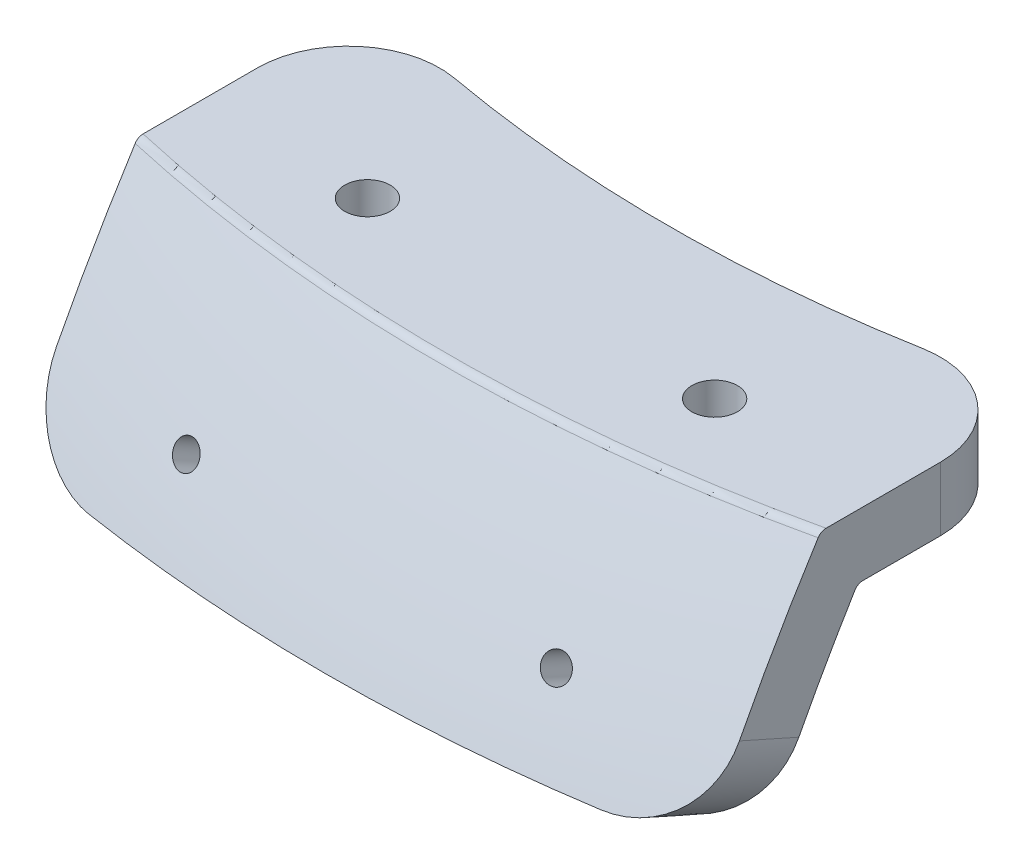
SolidWorks part; units mm, degrees
material "Polyether Polyol"
ref_plane "Front Plane" through (0, 0, 0) normal (0, 0, 1) x (1, 0, 0)
ref_plane "Top Plane" through (0, 0, 0) normal (0, 1, 0) x (1, 0, 0)
ref_plane "Right Plane" through (0, 0, 0) normal (1, 0, 0) x (0, 0, -1)
sketch "Sketch1" plane through (0, 0, 0) normal (1, 0, 0) x (0, 0, -1)
  line L0 (-182.3577, 155.0626) -> (-175.976, 152.1862) construction
  line L1 (-169.6296, 178.8688) -> (-144.7872, 178.8688) construction
  line L9 (-144.7872, 178.8688) -> (-144.7872, 171.8688) construction
  line L10 (-144.7872, 171.8688) -> (-165.7041, 171.8688) construction
  line L11 (-182.3577, 155.0626) -> (-175.976, 152.1862)
  line L12 (-169.6296, 178.8688) -> (-144.7872, 178.8688)
  line L13 (-144.7872, 178.8688) -> (-144.7872, 171.8688)
  line L14 (-144.7872, 171.8688) -> (-165.7041, 171.8688)
  line L15 (0, 0) -> (0, 72.8698) construction
  arc A5 (-165.7041, 171.8688) -> (-175.976, 152.1862) centre (0, 72.8698) ccw construction
  arc A6 (-169.6296, 178.8688) -> (-182.3577, 155.0626) centre (0, 72.8698) ccw construction
  arc A7 (-165.7041, 171.8688) -> (-175.976, 152.1862) centre (0, 72.8698) ccw
  arc A8 (-169.6296, 178.8688) -> (-182.3577, 155.0626) centre (0, 72.8698) ccw
revolve "Revolve1" add sketch "Sketch1" angle 30 mid plane about L15
sketch "Sketch2" plane through (0, 0, 0) normal (-1, 0, 0) x (0, 0, 1)
  line L0 (0, 72.8698) -> (171.9865, 160.5013) construction
  line L3 (0, -200000) -> (0, 218797.9879) construction
  arc A0 (175.976, 152.1862) -> (165.7041, 171.8688) centre (0, 72.8698) ccw construction
  dimension "D1" = 63
ref_plane "Plane1" through (0, 57.8508, -29.4764) normal (0, -0.891, 0.454) x (0, 0.454, 0.891)
sketch "Sketch4" plane through (0, 57.8508, -29.4764) normal (0, -0.891, 0.454) x (0, 0.454, 0.891)
  line L0 (200.4524, 17.5373) -> (239.1484, 20.9228) construction
  line L1 (200.3217, 19.0316) -> (239.0177, 22.4171)
  line L2 (200.3217, 19.0316) -> (200.4524, 17.5373)
  line L3 (33.0822, 0) -> (226.1072, 0) construction
  line L4 (200.4524, 17.5373) -> (239.1484, 20.9228)
  line L5 (239.0177, 22.4171) -> (239.1484, 20.9228)
  dimension "D1" = 3
  dimension "D2" = 5
revolve "Cut-Revolve1" cut sketch "Sketch4" angle 360 about L0
mirror "Mirror1" about plane through (0, 0, 0) normal (1, 0, 0) of "Cut-Revolve1"
sketch "Sketch5" plane through (0, 0, 0) normal (0, 1, 0) x (1, 0, 0)
  line L1 (37.4737, -139.8537) -> (-37.4737, -139.8537)
  line L2 (37.4737, -139.8537) -> (37.4737, -182.3577)
  line L3 (37.4737, -182.3577) -> (-37.4737, -182.3577)
  line L4 (-37.4737, -139.8537) -> (-37.4737, -182.3577)
  arc A0 (-47.1977, -176.1441) -> (47.1977, -176.1441) centre (0, 0) ccw construction
extrude "Cut-Extrude2" cut sketch "Sketch5" along normal through all flip side to cut
fillet "Fillet1" radius 10 4 edges at (-37.4737, 175.3688, 139.8537) (37.4737, 175.3688, 139.8537)
fillet "Fillet2" radius 1 2 edges at (0, 178.8688, 169.6296) (0, 171.8688, 165.7041)
sketch "Sketch6" plane through (0, 178.8688, 0) normal (0, 1, 0) x (1, 0, 0)
  line L0 (0, 0) -> (0, -158.6742) construction
  line L1 (-19.05, -158.6742) -> (19.05, -158.6742) construction
  circle A2 centre (19.05, -158.6742) radius 2.5
  circle A3 centre (-19.05, -158.6742) radius 2.5
  point P11 (0, -158.6742)
  dimension "D3" = 5
  dimension "D1" = 38.1
  dimension "D2" = 158.6742
extrude "Cut-Extrude3" cut sketch "Sketch6" against normal through all
